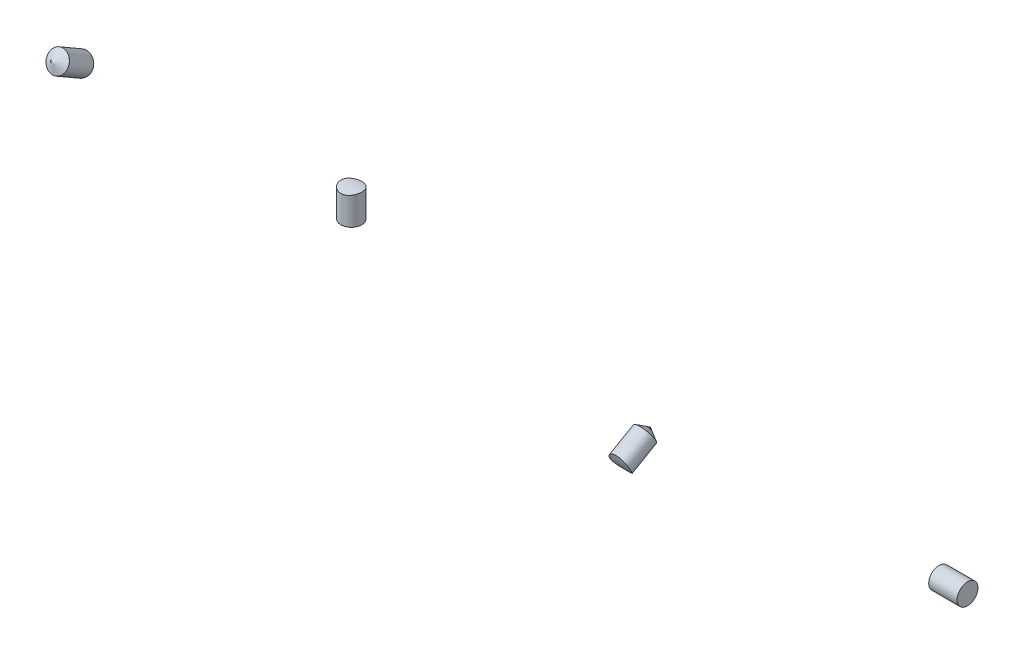
SolidWorks part; units mm, degrees
material "Custom Plastic"
ref_plane "Front Plane" through (0, 0, 0) normal (0, 0, 1) x (1, 0, 0)
ref_plane "Top Plane" through (0, 0, 0) normal (0, 1, 0) x (1, 0, 0)
ref_plane "Right Plane" through (0, 0, 0) normal (1, 0, 0) x (0, 0, -1)
sketch "Sketch1" plane through (0, 0, 0) normal (1, 0, 0) x (0, 0, -1)
  circle A0 centre (0, 0) radius 11.11
  dimension "D1" = 22.22
extrude "Boss-Extrude1" add sketch "Sketch1" along normal blind 304
hole_wizard "Ø3.0 (3) Diameter Hole2" positions "Sketch7" profile "Sketch6" hole size "Ø3.0" standard "ANSI Metric"
sketch "Sketch7" plane through (0, 0, 0) normal (-1, 0, 0) x (0, 0, 1)
  point P0 (0, 5.3)
  dimension "D1" = 5.3
sketch "Sketch6" plane through (0, 5.3, 0) normal (0, 1, 0) x (0, 0, 1)
  line L0 (0, 0) -> (0, 11.9013)
  line L1 (0, 11.9013) -> (1.5, 11)
  line L2 (1.5, 11) -> (1.5, 0)
  line L5 (1.5, 0) -> (0, 0)
  line L10 (0, 11.9013) -> (-1.5, 11) construction
  line L11 (0, -6.35) -> (0, 107.95) construction
  dimension "Hole Dia." = 3
  dimension "Hole Depth" = 11
  dimension "Drill Angle" = 118
ref_plane "Plane1" through (0, 11.11, 0) normal (0, 1, 0) x (1, 0, 0)
hole_wizard "13/64 (0.20313) Diameter Hole2" positions "Sketch11" profile "Sketch10" hole size "13/64" standard "ANSI Inch"
sketch "Sketch11" plane through (0, 11.11, 0) normal (0, 1, 0) x (1, 0, 0)
  point P1 (152, 0)
  dimension "D1" = 152
sketch "Sketch10" plane through (152, 11.11, 0) normal (1, 0, 0) x (0, 0, 1)
  line L0 (0, 0) -> (0, 8.5501)
  line L1 (0, 8.5501) -> (2.5798, 7)
  line L2 (2.5798, 7) -> (2.5798, 0)
  line L5 (2.5798, 0) -> (0, 0)
  line L10 (0, 8.5501) -> (-2.5798, 7) construction
  line L11 (0, -6.35) -> (0, 107.95) construction
  dimension "Hole Dia." = 5.1595
  dimension "Hole Depth" = 7
  dimension "Drill Angle" = 118
ref_plane "Plane2" through (0, -5.555, 9.6215) normal (0, -0.5, 0.866) x (-1, 0, 0)
ref_plane "Plane3" through (0, -5.555, -9.6215) normal (0, -0.5, -0.866) x (-1, 0, 0)
hole_wizard "13/64 (0.20313) Diameter Hole4" positions "Sketch15" profile "Sketch14" hole size "13/64" standard "ANSI Inch"
sketch "Sketch15" plane through (0, -5.555, -9.6215) normal (0, -0.5, -0.866) x (-1, 0, 0)
  point P0 (-76, 0)
  dimension "D1" = 76
sketch "Sketch14" plane through (76, -5.555, -9.6215) normal (1, 0, 0) x (0, 0.866, -0.5)
  line L0 (0, 0) -> (0, 8.5501)
  line L1 (0, 8.5501) -> (2.5798, 7)
  line L2 (2.5798, 7) -> (2.5798, 0)
  line L5 (2.5798, 0) -> (0, 0)
  line L10 (0, 8.5501) -> (-2.5798, 7) construction
  line L11 (0, -6.35) -> (0, 107.95) construction
  dimension "Hole Dia." = 5.1595
  dimension "Hole Depth" = 7
  dimension "Drill Angle" = 118
hole_wizard "13/64 (0.20313) Diameter Hole5" positions "Sketch17" profile "Sketch16" hole size "13/64" standard "ANSI Inch"
sketch "Sketch17" plane through (0, -5.555, 9.6215) normal (0, -0.5, 0.866) x (-1, 0, 0)
  point P0 (-228, 0)
  dimension "D1" = 228
sketch "Sketch16" plane through (228, -5.555, 9.6215) normal (1, 0, 0) x (0, -0.866, -0.5)
  line L0 (0, 0) -> (0, 8.5501)
  line L1 (0, 8.5501) -> (2.5798, 7)
  line L2 (2.5798, 7) -> (2.5798, 0)
  line L5 (2.5798, 0) -> (0, 0)
  line L10 (0, 8.5501) -> (-2.5798, 7) construction
  line L11 (0, -6.35) -> (0, 107.95) construction
  dimension "Hole Dia." = 5.1595
  dimension "Hole Depth" = 7
  dimension "Drill Angle" = 118
hole_wizard "13/64 (0.20313) Diameter Hole6" positions "Sketch19" profile "Sketch18" hole size "13/64" standard "ANSI Inch"
sketch "Sketch19" plane through (304, 0, 0) normal (1, 0, 0) x (0, 0, -1)
  point P0 (0, 0)
sketch "Sketch18" plane through (304, 0, 0) normal (0, 1, 0) x (0, 0, -1)
  line L0 (0, 0) -> (0, 8.5501)
  line L1 (0, 8.5501) -> (2.5798, 7)
  line L2 (2.5798, 7) -> (2.5798, 0)
  line L5 (2.5798, 0) -> (0, 0)
  line L10 (0, 8.5501) -> (-2.5798, 7) construction
  line L11 (0, -6.35) -> (0, 107.95) construction
  dimension "Hole Dia." = 5.1595
  dimension "Hole Depth" = 7
  dimension "Drill Angle" = 118
sketch "Sketch20" plane through (0, 0, 0) normal (-1, 0, 0) x (0, 0, 1)
  circle A0 centre (0, 0) radius 11.11
  circle A1 centre (0, 0) radius 11.11
sketch "Sketch22" plane through (0, 0, 0) normal (1, 0, 0) x (0, 0, -1)
  circle A0 centre (0, 0) radius 11.11
  dimension "D1" = 22.22
extrude "Boss-Extrude5" add sketch "Sketch22" along normal blind 304 separate body
delete or keep bodies "Body-Delete/Keep 1" type delete bodies bodies 113
sketch "Sketch23" plane through (304, 0, 0) normal (1, 0, 0) x (0, 0, -1)
  circle A0 centre (0, 0) radius 11.11
extrude "Boss-Extrude6" add sketch "Sketch23" against normal blind 264 separate body
combine bodies "Combine3" operation type subtract main body 119 bodies to subtract 109
